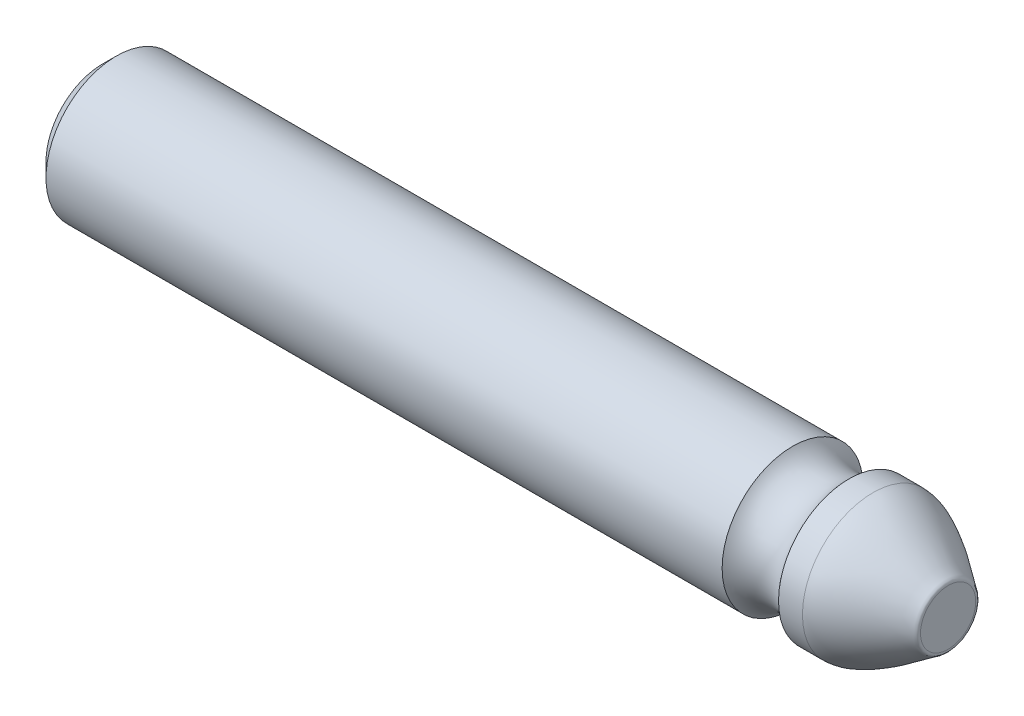
SolidWorks part; units mm, degrees
material "Alloy Steel"
ref_plane "Front" through (0, 0, 0) normal (0, 0, 1) x (1, 0, 0)
ref_plane "Top" through (0, 0, 0) normal (0, 1, 0) x (1, 0, 0)
ref_plane "Right" through (0, 0, 0) normal (1, 0, 0) x (0, 0, -1)
sketch "Sketch1" plane through (0, 0, 0) normal (0, 0, 1) x (1, 0, 0)
  line L0 (-19.05, 0) -> (19.05, 0) construction
  line L1 (19.05, 3.175) -> (19.05, -3.175) construction
  line L2 (-19.05, 3.175) -> (-19.05, -3.175) construction
  dimension "Length" = 38.1
  dimension "Diameter" = 6.35
sketch "Sketch2" plane through (0, 0, 0) normal (1, 0, 0) x (0, 0, -1)
  circle A0 centre (0, 0) radius 3.175
extrude "Extrude1" add sketch "Sketch2" against normal up to vertex (19.05 mm away) and the other way up to vertex (19.05 mm away) up to point (-19.05, 3.175, 0) other way up to point (19.05, 3.175, 0)
chamfer "Chamfer1" distance 0.635 angle 45 2 edges at (19.05, 0, -3.175) (-19.05, 0, -3.175)
sketch "Sketch3" plane through (0, 0, 0) normal (0, 0, 1) x (1, 0, 0)
  line L0 (-19.05, 0) -> (19.05, 0) construction
  line L1 (-19.05, 2.54) -> (-19.05, -2.54) construction
  line L2 (19.05, -2.54) -> (19.05, 2.54) construction
  line L3 (18.415, 3.175) -> (-18.415, 3.175) construction
  line L4 (15.6622, 3.175) -> (14.5842, 3.175)
  line L5 (16.629, 3.175) -> (14.655, 3.175) construction
  line L6 (19.05, 0.802) -> (19.05, 1.6965) construction
  line L7 (19.05, 1.2434) -> (19.05, 3.175)
  line L8 (19.05, 3.175) -> (15.6622, 3.175)
  circle A0 centre (13.3142, 4.1275) radius 1.5875
  spline S0 degree 3 poles (15.6622, 3.175) (16.6428, 3.175) (18.614, 1.6311) (19.0441, 1.3825) (19.05, 1.3487) (19.05, 1.2434) knots 0 0 0 0 0.565725 0.665725 1 1 1 1
  dimension "D1" = 3.175
  dimension "D2" = 0.635
revolve "Cut-Revolve1" cut sketch "Sketch3" angle 360 about L0 region at (13.3142, 4.1275, 0) region at (18.092, 2.592, 0)
equation "\"D1@Chamfer1\" = \"Diameter@Sketch1\"*.1"
